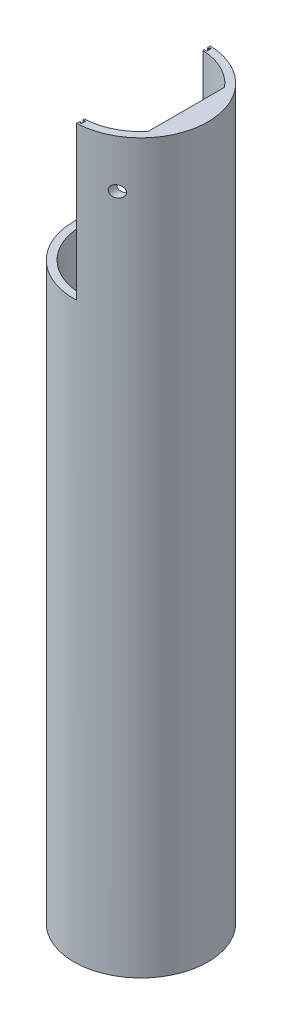
SolidWorks part; units mm, degrees
ref_plane "Front Plane" through (0, 0, 0) normal (0, 0, 1) x (1, 0, 0)
ref_plane "Top Plane" through (0, 0, 0) normal (0, 1, 0) x (1, 0, 0)
ref_plane "Right Plane" through (0, 0, 0) normal (1, 0, 0) x (0, 0, -1)
sketch "Sketch3" plane through (0, 0, 0) normal (0, 1, 0) x (1, 0, 0)
  circle A0 centre (0, 0) radius 17.5
  circle A1 centre (0, 0) radius 15.5
  dimension "D1" = 35
  dimension "D2" = 31
extrude "Boss-Extrude1" add sketch "Sketch3" along normal blind 150
sketch "Sketch4" plane through (0, 150, 0) normal (0, 1, 0) x (1, 0, 0)
  line L0 (0.6704, 17.4872) -> (0.6704, 16.6614)
  line L1 (0.6704, 16.6614) -> (0.9998, 16.6614)
  line L2 (1.343, 16.9583) -> (1.3406, 15.8306)
  line L3 (1.3406, 15.8306) -> (0.6552, 15.8306)
  line L4 (0.6552, 15.8306) -> (0.6552, 15.4861)
  line L5 (0.9998, 16.6614) -> (0.9998, 16.9583)
  line L6 (0.9998, 16.9583) -> (1.343, 16.9583)
  line L7 (0.9998, -16.9583) -> (1.343, -16.9583)
  line L8 (0, 0) -> (21.7415, 0) construction
  line L9 (0.9998, -16.6614) -> (0.9998, -16.9583)
  line L10 (0.9998, -16.9583) -> (1.343, -16.9583)
  line L11 (0.6552, -15.8306) -> (0.6552, -15.4861)
  line L12 (1.3406, -15.8306) -> (0.6552, -15.8306)
  line L13 (1.343, -16.9583) -> (1.3406, -15.8306)
  line L14 (0.6704, -16.6614) -> (0.9998, -16.6614)
  line L15 (0.6704, -17.4872) -> (0.6704, -16.6614)
  line L16 (0.6704, -17.4872) -> (0.6704, -16.6614)
  circle A0 centre (0, 0) radius 17.5 construction
  circle A3 centre (0, 0) radius 17.5
  arc A4 (0.6704, -17.4872) -> (0.6704, 17.4872) centre (0, 0) ccw
  circle A5 centre (0, 0) radius 15.5 construction
  circle A6 centre (0, 0) radius 15.5
  arc A7 (0.6552, -15.4861) -> (0.6552, 15.4861) centre (0, 0) ccw
  circle M11 centre (0, 0) radius 17.5
  circle M12 centre (0, 0) radius 15.5
  dimension "D2" = 0
  dimension "D5" = 0.3294
  dimension "D6" = 0.8258
  dimension "D8" = 0.3432
  dimension "D1" = 0
extrude "Boss-Extrude2" add sketch "Sketch4" along normal blind 20 contours L8 A4 L0 L1 L5 L6 L2 L3 L4 M12 | L8 A7 L11 L12 L13 L7 L9 L14 L15 M11 region at (12.4342, 150, -11.9667) region at (12.4342, 150, 11.9667)
sketch "Sketch5" plane through (0, 170, 0) normal (0, 1, 0) x (1, 0, 0)
  line L14 (11.8427, 10) -> (11.8427, -10)
  line L28 (0.6552, -15.4861) -> (0.6552, -15.8306)
  line L29 (0.6552, -15.8306) -> (1.3406, -15.8306)
  line L30 (1.3406, -15.8306) -> (1.343, -16.9583)
  line L31 (1.343, -16.9583) -> (0.9998, -16.9583)
  line L32 (0.9998, -16.9583) -> (0.9998, -16.6614)
  line L33 (0.9998, -16.6614) -> (0.6704, -16.6614)
  line L34 (0.6704, -16.6614) -> (0.6704, -17.4872)
  line L35 (0.6704, 17.4872) -> (0.6704, 16.6614)
  line L36 (0.6704, 16.6614) -> (0.9998, 16.6614)
  line L37 (0.9998, 16.6614) -> (0.9998, 16.9583)
  line L38 (0.9998, 16.9583) -> (1.343, 16.9583)
  line L39 (1.343, 16.9583) -> (1.3406, 15.8306)
  line L40 (1.3406, 15.8306) -> (0.6552, 15.8306)
  line L41 (0.6552, 15.8306) -> (0.6552, 15.4861)
  line L42 (0.6552, -15.4861) -> (0.6552, -15.8306)
  line L43 (0.6552, -15.8306) -> (1.3406, -15.8306)
  line L44 (1.3406, -15.8306) -> (1.343, -16.9583)
  line L45 (1.343, -16.9583) -> (0.9998, -16.9583)
  line L46 (0.9998, -16.9583) -> (0.9998, -16.6614)
  line L47 (0.9998, -16.6614) -> (0.6704, -16.6614)
  line L48 (0.6704, -16.6614) -> (0.6704, -17.4872)
  line L49 (0.6704, 17.4872) -> (0.6704, 16.6614)
  line L50 (0.6704, 16.6614) -> (0.9998, 16.6614)
  line L51 (0.9998, 16.6614) -> (0.9998, 16.9583)
  line L52 (0.9998, 16.9583) -> (1.343, 16.9583)
  line L53 (1.343, 16.9583) -> (1.3406, 15.8306)
  line L54 (1.3406, 15.8306) -> (0.6552, 15.8306)
  line L55 (0.6552, 15.8306) -> (0.6552, 15.4861)
  arc A3 (11.8427, 10) -> (0.6552, 15.4861) centre (0, 0) ccw
  arc A4 (0.6552, -15.4861) -> (0.6552, 15.4861) centre (0, 0) ccw
  arc A5 (0.6704, -17.4872) -> (0.6704, 17.4872) centre (0, 0) ccw
  arc A6 (0.6552, -15.4861) -> (11.8427, -10) centre (0, 0) ccw
  arc A7 (0.6704, -17.4872) -> (0.6704, 17.4872) centre (0, 0) ccw
  arc A8 (0.6552, -15.4861) -> (0.6552, 15.4861) centre (0, 0) ccw
  arc A9 (0.6552, -15.4861) -> (11.8427, -10) centre (0, 0) ccw
  arc M19 (0.6552, 15.4861) -> (0.6552, -15.4861) centre (0, 0) cw
  line M20 (0.6552, -15.4861) -> (0.6552, -15.8306)
  line M21 (0.6552, -15.8306) -> (1.3406, -15.8306)
  line M22 (1.3406, -15.8306) -> (1.343, -16.9583)
  line M23 (1.343, -16.9583) -> (0.9998, -16.9583)
  line M24 (0.9998, -16.9583) -> (0.9998, -16.6614)
  line M25 (0.9998, -16.6614) -> (0.6704, -16.6614)
  line M26 (0.6704, -16.6614) -> (0.6704, -17.4872)
  arc M27 (0.6704, -17.4872) -> (0.6704, 17.4872) centre (0, 0) ccw
  line M28 (0.6704, 17.4872) -> (0.6704, 16.6614)
  line M29 (0.6704, 16.6614) -> (0.9998, 16.6614)
  line M30 (0.9998, 16.6614) -> (0.9998, 16.9583)
  line M31 (0.9998, 16.9583) -> (1.343, 16.9583)
  line M32 (1.343, 16.9583) -> (1.3406, 15.8306)
  line M33 (1.3406, 15.8306) -> (0.6552, 15.8306)
  line M34 (0.6552, 15.8306) -> (0.6552, 15.4861)
  dimension "D2" = 20
  dimension "D1" = 0
  dimension "D3" = 0
extrude "Boss-Extrude3" add sketch "Sketch5" along normal blind 20 contours M34 M19 M20 M21 M22 M23 M24 M25 M26 M27 M28 M29 M30 M31 M32 M33 | L14 M19 region at (13.3215, 170, 0) region at (6.9954, 170, -14.2653)
sketch "Sketch6" plane through (11.8427, 0, 0) normal (-1, 0, 0) x (0, 0, 1)
  line L0 (-10, 190) -> (10, 190) construction
  line L1 (-8.7, 180) -> (-3.7, 180)
  line L2 (-8.7, 180) -> (-8.7, 175)
  line L3 (-8.7, 175) -> (-3.7, 175)
  line L4 (-3.7, 180) -> (-3.7, 175)
  line L5 (-8.7, 180) -> (-3.7, 175) construction
  line L6 (-8.7, 175) -> (-3.7, 180) construction
  line L9 (0, 190) -> (0, 170) construction
  line L10 (-10, 170) -> (10, 170) construction
  line L11 (-10, 190) -> (-10, 170) construction
  line L12 (8.7, 175) -> (3.7, 180) construction
  line L13 (8.7, 180) -> (3.7, 175) construction
  line L14 (3.7, 180) -> (3.7, 175)
  line L15 (8.7, 175) -> (3.7, 175)
  line L16 (8.7, 180) -> (8.7, 175)
  line L17 (8.7, 180) -> (3.7, 180)
  point P0 (-6.2, 177.5)
  point P17 (6.2, 177.5)
  dimension "D1" = 10
  dimension "D2" = 5
  dimension "D3" = 5
  dimension "D4" = 1.3
extrude "Boss-Extrude4" add sketch "Sketch6" along normal blind 6
sketch "Sketch7" plane through (0, 0, -8.7) normal (0, 0, -1) x (-1, 0, 0)
  line L4 (-11.8427, 180) -> (-5.8427, 175) construction
  line L5 (-5.8427, 180) -> (-11.8427, 175) construction
  line L8 (-11.8427, 180) -> (-11.8427, 175)
  line L9 (-11.8427, 175) -> (-5.8427, 175)
  line L10 (-5.8427, 175) -> (-5.8427, 180)
  line L11 (-5.8427, 180) -> (-11.8427, 180)
  line L12 (-11.8427, 180) -> (-11.8427, 175)
  line L13 (-11.8427, 175) -> (-5.8427, 175)
  line L14 (-5.8427, 175) -> (-5.8427, 180)
  line L15 (-5.8427, 180) -> (-11.8427, 180)
  circle A0 centre (-8.8427, 177.5) radius 1.5
  dimension "D2" = 3
  dimension "D1" = 0
extrude "Cut-Extrude2" cut sketch "Sketch7" against normal blind 50 contours A0
sketch "Sketch9" plane through (11.8427, 0, 0) normal (-1, 0, 0) x (0, 0, 1)
  line L0 (-3.7, 180) -> (3.7, 175) construction
  line L30 (3, 172.5) -> (-3, 172.5)
  line L31 (3, 172.5) -> (3, 182.5)
  line L32 (3, 182.5) -> (-3, 182.5)
  line L33 (-3, 172.5) -> (-3, 182.5)
  line L34 (3, 172.5) -> (-3, 182.5) construction
  line L35 (3, 182.5) -> (-3, 172.5) construction
  point P2 (0, 177.5)
  point P10 (0, 177.5)
  dimension "D1" = 10
  dimension "D2" = 6
extrude "Cut-Extrude3" cut sketch "Sketch9" against normal blind 2
fillet "Fillet3" radius 3.2 4 edges at (13.8427, 177.5, -3) (13.8427, 172.5, 0) (13.8427, 177.5, 3) (13.8427, 182.5, 0)
sketch "Sketch11" plane through (11.8427, 0, 0) normal (-1, 0, 0) x (0, 0, 1)
  line L4 (3, 182.5) -> (-3, 182.5) construction
  line L5 (-3, 182.5) -> (-3, 172.5) construction
  line L6 (3, 172.5) -> (3, 182.5) construction
  line L7 (-3, 172.5) -> (3, 172.5) construction
  line L8 (-10, 170) -> (10, 170)
  line L9 (10, 170) -> (10, 190)
  line L10 (10, 190) -> (-10, 190)
  line L11 (-10, 190) -> (-10, 170)
  line L12 (-10, 170) -> (10, 170)
  line L13 (10, 170) -> (10, 190)
  line L14 (10, 190) -> (-10, 190)
  line L15 (-10, 190) -> (-10, 170)
  line L16 (-3, 172.5) -> (3, 172.5)
  line L17 (3, 172.5) -> (3, 182.5)
  line L18 (-3, 182.5) -> (-3, 172.5)
  line L19 (3, 182.5) -> (-3, 182.5)
  point P0 (0, 172.5)
  dimension "D2" = 6
  dimension "D3" = 10
  dimension "D1" = 0
